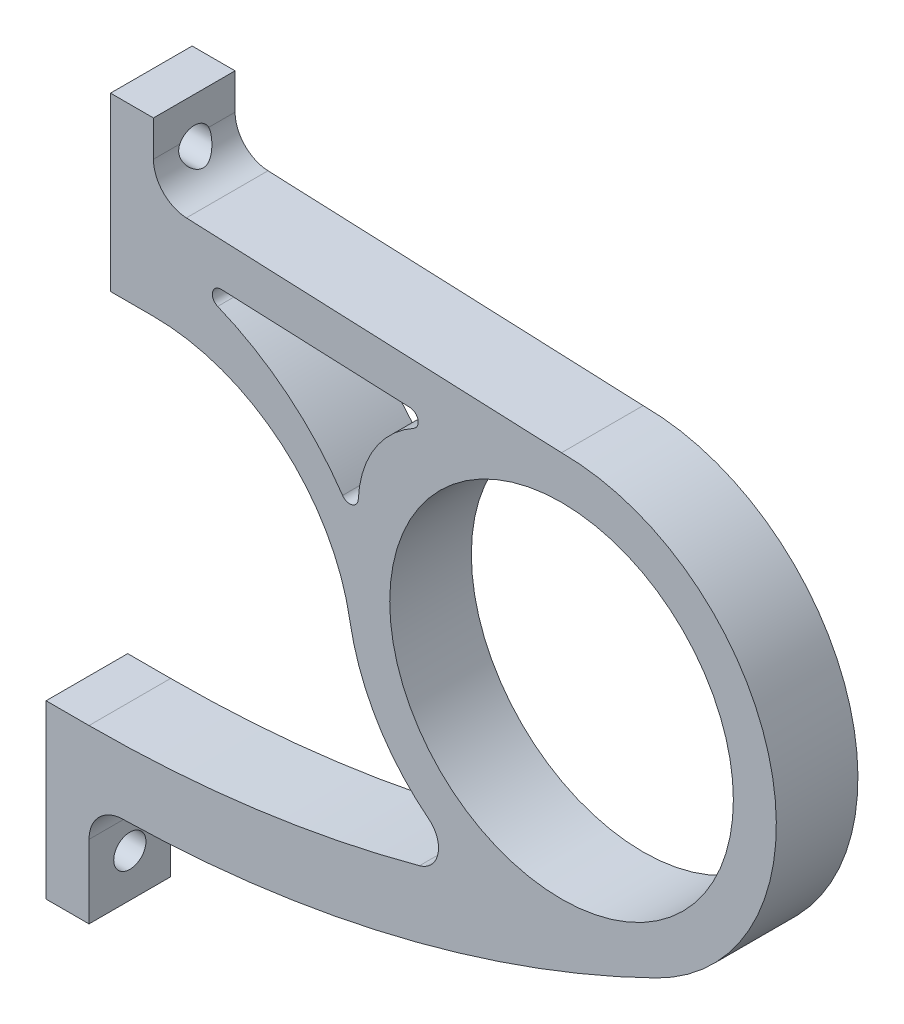
SolidWorks part; units mm, degrees
material "6061 Alloy"
ref_plane "Front Plane" through (0, 0, 0) normal (0, 0, 1) x (1, 0, 0)
ref_plane "Top Plane" through (0, 0, 0) normal (0, 1, 0) x (1, 0, 0)
ref_plane "Right Plane" through (0, 0, 0) normal (1, 0, 0) x (0, 0, -1)
sketch "Sketch1" plane through (0, 0, 0) normal (0, 0, 1) x (1, 0, 0)
  line L0 (-133.35, 88.9) -> (-133.35, 38.1)
  line L1 (-133.35, 38.1) -> (-120.65, 38.1)
  line L2 (-133.35, 88.9) -> (-120.65, 88.9)
  line L3 (-120.65, 88.9) -> (-120.65, 68.58)
  line L4 (-120.65, 68.58) -> (0, 63.5)
  line L5 (-152.4, -76.2) -> (-139.7, -76.2)
  line L6 (-152.4, -76.2) -> (-152.4, -127)
  line L7 (-152.4, -127) -> (-139.7, -127)
  line L8 (-139.7, -127) -> (-139.7, -95.25)
  line L9 (-26.7873, 51.9166) -> (-129.54, 56.2431)
  circle A1 centre (0, 0) radius 50.8
  arc A7 (27.94, -57.0229) -> (0, 63.5) centre (0, 0) ccw
  arc A13 (-139.7, -95.25) -> (27.94, -57.0229) centre (-136.9997, 279.6033) ccw
  arc A14 (-62.5737, -10.8063) -> (-25.2005, -58.2854) centre (0, 0) ccw
  arc A15 (-25.2005, -58.2854) -> (-139.7, -76.2) centre (-139.7, 298.6631) cw
  arc A16 (-62.5737, -10.8063) -> (-120.65, 38.1) centre (-120.65, -20.8359) ccw
  arc A17 (-57.4211, 7.0272) -> (-129.54, 56.2431) centre (-133.0154, -26.2976) ccw
  arc A18 (-26.7873, 51.9166) -> (-57.4211, 7.0272) centre (-28.1338, 19.9381) ccw
  point P19 (0, 0)
  point P24 (-93.9964, 54.9528)
  point P26 (-105.8732, 44.7185)
  point P28 (-59.882, 2.7705)
  point P29 (0, 0)
  point P30 (-63.7989, 20.8384)
  point P31 (-84.2675, 39.4118)
  point P33 (-67.7157, 26.0188)
  point P34 (-58.3658, 29.0512)
  point P35 (0, 0)
  point P36 (0, 0)
  point P37 (0, 0)
  point P38 (-50.0228, 8.8522)
  point P39 (-44.1253, -16.6919)
  point P40 (-125.5524, 56.0752)
  point P41 (-59.099, 3.8423)
  point P42 (-32.0521, 52.1383)
  point P43 (-126.5684, 56.1179)
  point P44 (-28.1338, -56.8913)
  dimension "D2" = 101.6
  dimension "D13" = 12.7
  dimension "D14" = 7.62
  dimension "D25" = 12.7
  dimension "D3" = 50.8
  dimension "D4" = 12.7
  dimension "D5" = 20.32
  dimension "D6" = 133.35
  dimension "D7" = 152.4
  dimension "D8" = 12.7
  dimension "D9" = 50.8
  dimension "D10" = 31.75
  dimension "D11" = 88.9
  dimension "D12" = 127
  dimension "D15" = 10.16
  dimension "D16" = 8.89
  dimension "D19" = 167.64
extrude "Boss-Extrude1" add sketch "Sketch1" along normal blind 24.13
fillet "Fillet1" radius 10.16 2 edges at (-139.7, -95.25, 12.065) (-120.65, 68.58, 12.065)
fillet "Fillet2" radius 2.54 3 edges at (-57.4211, 7.0272, 12.065) (-26.7873, 51.9166, 12.065) (-129.54, 56.2431, 12.065)
fillet "Fillet3" radius 7.62 1 edges at (-25.2005, -58.2854, 12.065)
sketch "Sketch2" plane through (-152.4, 0, 0) normal (-1, 0, 0) x (0, 0, 1)
  line L0 (24.13, 88.9) -> (0, 88.9) construction
  line L1 (24.13, -127) -> (0, -127) construction
  circle A0 centre (12.065, -114.3) radius 4.7625
  circle A1 centre (12.065, 76.2) radius 4.7625
  point P6 (12.065, 88.9)
  dimension "D1" = 9.525
  dimension "D2" = 12.7
  dimension "D3" = 12.7
extrude "Cut-Extrude1" cut sketch "Sketch2" against normal through all
